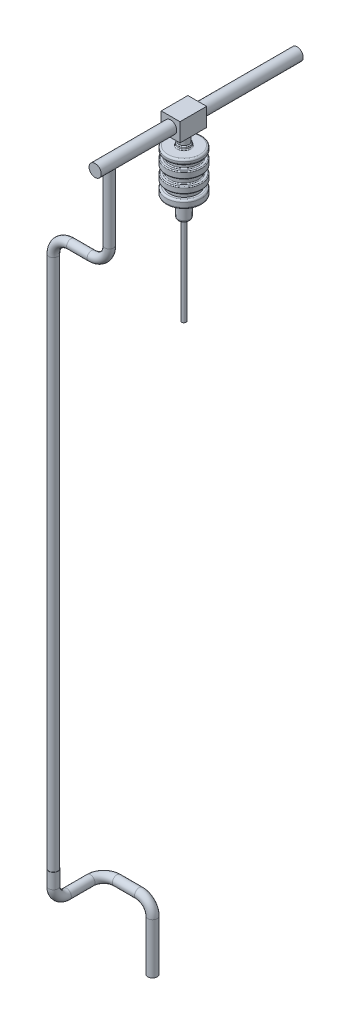
SolidWorks part; units mm, degrees
ref_plane "Alzado" through (0, 0, 0) normal (0, 0, 1) x (1, 0, 0)
ref_plane "Planta" through (0, 0, 0) normal (0, 1, 0) x (1, 0, 0)
ref_plane "Vista lateral" through (0, 0, 0) normal (1, 0, 0) x (0, 0, -1)
sketch "Croquis1" plane through (0, 0, 0) normal (0, 0, 1) x (1, 0, 0)
  line L0 (0, 0) -> (0, 150) construction
  line L1 (0, 0) -> (8.3493, 0)
  line L2 (13.3493, 5) -> (13.3493, 40.6115)
  line L3 (18.3493, 45.6115) -> (36, 45.6115)
  line L4 (0, 150) -> (11.3493, 150)
  line L5 (40, 138.8463) -> (40, 134.9395)
  line L6 (13.3493, 148) -> (13.3493, 144.8463)
  line L7 (15.3493, 142.8463) -> (36, 142.8463)
  line L8 (36, 130.9395) -> (33.6016, 130.9395)
  line L9 (31.6016, 128.9395) -> (31.6016, 121.4919)
  line L10 (33.6016, 119.4919) -> (38, 119.4919)
  line L11 (40, 117.4919) -> (40, 106.1197)
  line L12 (38, 104.1197) -> (33.6016, 104.1197)
  line L13 (31.6016, 102.1197) -> (31.6016, 91.6517)
  line L14 (33.6016, 89.6517) -> (38, 89.6517)
  line L15 (40, 87.6517) -> (40, 77)
  line L16 (38, 75) -> (33.6016, 75)
  line L17 (31.6016, 73) -> (31.6016, 63.4285)
  line L18 (31.6016, 63.4285) -> (36, 63.4285)
  line L19 (40, 59.4285) -> (40, 49.6115)
  line L20 (0, 0) -> (0, 150) construction
  line L21 (0, 0) -> (0, 150)
  arc A0 (36, 63.4285) -> (40, 59.4285) centre (36, 59.4285) cw
  arc A1 (36, 45.6115) -> (40, 49.6115) centre (36, 49.6115) ccw
  arc A2 (36, 142.8463) -> (40, 138.8463) centre (36, 138.8463) cw
  arc A3 (40, 134.9395) -> (36, 130.9395) centre (36, 134.9395) cw
  arc A4 (13.3493, 148) -> (11.3493, 150) centre (11.3493, 148) ccw
  arc A5 (13.3493, 144.8463) -> (15.3493, 142.8463) centre (15.3493, 144.8463) ccw
  arc A6 (40, 77) -> (38, 75) centre (38, 77) cw
  arc A7 (33.6016, 75) -> (31.6016, 73) centre (33.6016, 73) ccw
  arc A8 (33.6016, 130.9395) -> (31.6016, 128.9395) centre (33.6016, 128.9395) ccw
  arc A9 (31.6016, 121.4919) -> (33.6016, 119.4919) centre (33.6016, 121.4919) ccw
  arc A10 (33.6016, 104.1197) -> (31.6016, 102.1197) centre (33.6016, 102.1197) ccw
  arc A11 (31.6016, 91.6517) -> (33.6016, 89.6517) centre (33.6016, 91.6517) ccw
  arc A12 (38, 89.6517) -> (40, 87.6517) centre (38, 87.6517) cw
  arc A13 (40, 106.1197) -> (38, 104.1197) centre (38, 106.1197) cw
  arc A14 (38, 119.4919) -> (40, 117.4919) centre (38, 117.4919) cw
  arc A15 (13.3493, 40.6115) -> (18.3493, 45.6115) centre (18.3493, 40.6115) cw
  arc A16 (8.3493, 0) -> (13.3493, 5) centre (8.3493, 5) ccw
  point P25 (40, 45.6115)
  dimension "D3" = 4
  dimension "D4" = 2
  dimension "D5" = 5
  dimension "D6" = 5
  dimension "D1" = 150
  dimension "D2" = 40
revolve "Revolución1" add sketch "Croquis1" angle 360 about L21
sketch "Croquis2" plane through (0, 150, 0) normal (0, 1, 0) x (1, 0, 0)
  circle A0 centre (0, 0) radius 11.3493
extrude "Saliente-Extruir1" add sketch "Croquis2" along normal blind 30
sketch "Croquis3" plane through (0, 0, 0) normal (0, 0, 1) x (1, 0, 0)
  line L1 (21.0986, 214.2333) -> (-21.0986, 214.2333)
  line L2 (21.0986, 214.2333) -> (21.0986, 172.8099)
  line L3 (21.0986, 172.8099) -> (-21.0986, 172.8099)
  line L4 (-21.0986, 214.2333) -> (-21.0986, 172.8099)
  line L5 (21.0986, 214.2333) -> (-21.0986, 172.8099) construction
  line L6 (21.0986, 172.8099) -> (-21.0986, 214.2333) construction
  circle A0 centre (0, 193.5216) radius 13.7
  point P0 (0, 193.5216)
  dimension "D1" = 27.4
extrude "Saliente-Extruir2" add sketch "Croquis3" along normal blind 30 and the other way blind 30
sketch "Croquis4" plane through (0, 0, 0) normal (0, 0, 1) x (1, 0, 0)
  circle A0 centre (0, 193.5216) radius 13.7
extrude "Saliente-Extruir3" add sketch "Croquis4" along normal blind 200 and the other way blind 200
sketch "Croquis5" plane through (0, 0, 0) normal (0, -1, 0) x (1, 0, 0)
  circle A0 centre (0, 0) radius 5
  dimension "D1" = 10
extrude "Saliente-Extruir4" add sketch "Croquis5" along normal blind 200
ref_plane "Plano1" through (0, 0, 200) normal (0, 0, 1) x (1, 0, 0)
ref_plane "Plano2" through (0, 190, 0) normal (0, 1, 0) x (1, 0, 0)
sketch "Croquis6" plane through (0, 190, 0) normal (0, 1, 0) x (1, 0, 0)
  circle A0 centre (0, -167.901) radius 10.0766
sketch3d "Croquis3D1"
  line L0 (0, 190, 167.901) -> (0, -1083.9314, 167.901) construction
  line L1 (0, -1083.9314, 167.901) -> (-112.9539, -1083.9314, 167.901) construction
  line L2 (-112.9539, -1083.9314, 167.901) -> (-112.9539, -937.1576, 167.901) construction
  line L3 (0, 190, 167.901) -> (0, 31.5276, 167.901)
  line L4 (-40, -8.4724, 167.901) -> (-86.1662, -8.4724, 167.901)
  line L5 (-126.1662, -48.4724, 167.901) -> (-126.1662, -1247.1428, 167.901)
  arc A0 (-86.1662, -8.4724, 167.901) -> (-126.1662, -48.4724, 167.901) centre (-86.1662, -48.4724, 167.901) ccw
  arc A1 (0, 31.5276, 167.901) -> (-40, -8.4724, 167.901) centre (-40, 31.5276, 167.901) ccw
  point P10 (-126.1662, -8.4724, 167.901)
  point P11 (-86.1662, -48.4724, 207.901)
  point P14 (0, -8.4724, 167.901)
  point P15 (-40, 31.5276, 127.901)
  dimension "D1" = 40
sweep "Barrer1" add profiles "Croquis6" path "Croquis3D1"
sketch3d "Croquis3D2"
  line L0 (-126.1662, -1247.1428, 167.901) -> (-126.1662, -1281.2412, 167.901)
  line L1 (-126.1662, -48.4724, 167.901) -> (-126.1662, -1247.1428, 167.901) construction
  line L2 (-126.1662, -1311.2412, 137.901) -> (-126.1662, -1311.2412, 84.5337)
  line L4 (-96.1662, -1311.2412, 54.5337) -> (-46.1662, -1311.2412, 54.5337)
  line L5 (-16.1662, -1341.2412, 54.5337) -> (-16.1662, -1454.8261, 54.5337)
  arc A0 (-126.1662, -1281.2412, 167.901) -> (-126.1662, -1311.2412, 137.901) centre (-126.1662, -1281.2412, 137.901) ccw
  arc A1 (-46.1662, -1311.2412, 54.5337) -> (-16.1662, -1341.2412, 54.5337) centre (-46.1662, -1341.2412, 54.5337) ccw
  arc A2 (-126.1662, -1311.2412, 84.5337) -> (-96.1662, -1311.2412, 54.5337) centre (-96.1662, -1311.2412, 84.5337) ccw
  point P8 (-126.1662, -1311.2412, 167.901)
  point P10 (-96.1662, -1281.2412, 137.901)
  point P13 (-16.1662, -1311.2412, 54.5337)
  point P14 (-46.1662, -1341.2412, 24.5337)
  point P17 (-126.1662, -1311.2412, 54.5337)
  point P18 (-96.1662, -1341.2412, 84.5337)
  dimension "D2" = 30
  dimension "D1" = 110
sweep "Barrer2" add path "Croquis3D2" circular profile diameter 21 parameters "D3"=21
sketch "Croquis7" plane through (0, 0, -200) normal (0, 0, -1) x (-1, 0, 0)
  circle A0 centre (0, 193.5216) radius 13.7
extrude "Saliente-Extruir5" add sketch "Croquis7" along normal blind 55
